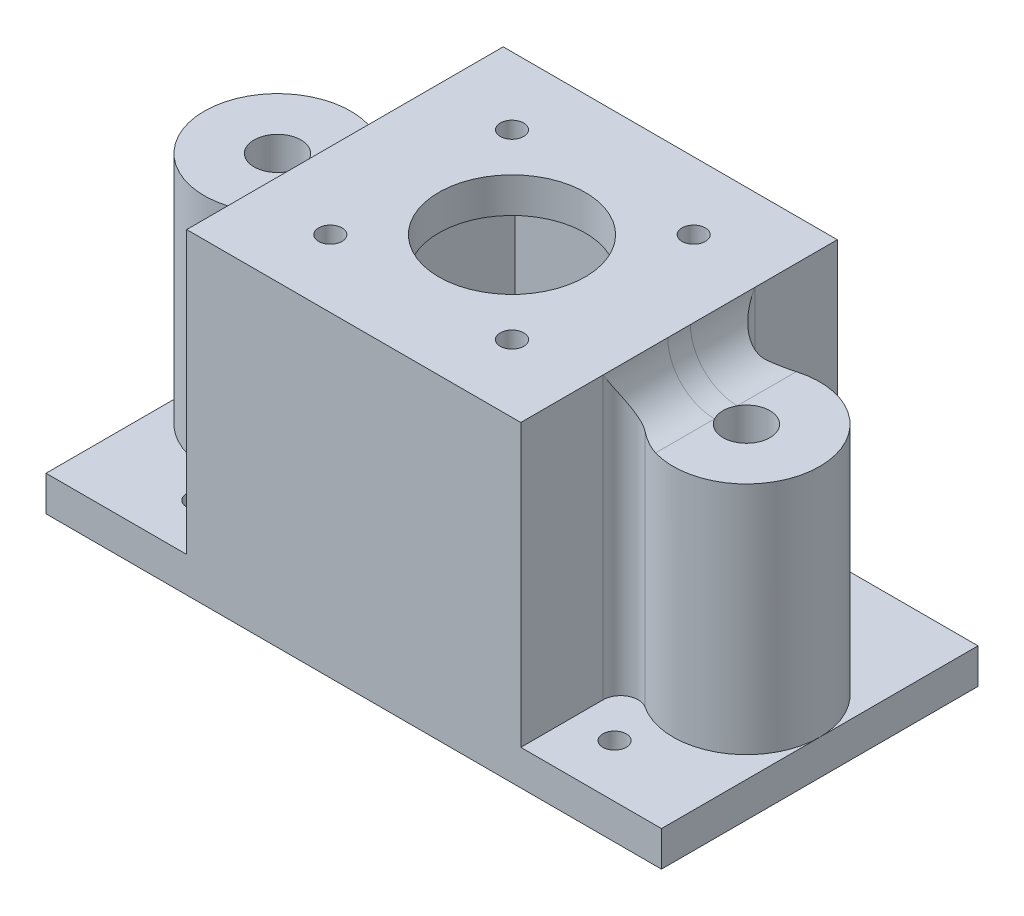
SolidWorks part; units mm, degrees
material "ABS"
ref_plane "Plano frontal" through (0, 0, 0) normal (0, 0, 1) x (1, 0, 0)
ref_plane "Plano superior" through (0, 0, 0) normal (0, 1, 0) x (1, 0, 0)
ref_plane "Plano direito" through (0, 0, 0) normal (1, 0, 0) x (0, 0, -1)
sketch "Esboço1" plane through (0, 0, 0) normal (0, 0, 1) x (1, 0, 0)
  line L0 (-28.5, 54) -> (28.5, 54)
  line L1 (28.5, 54) -> (28.5, 6)
  line L2 (52.5, 6) -> (28.5, 6)
  line L3 (52.5, 6) -> (52.5, 0)
  line L4 (52.5, 0) -> (22.5, 0)
  line L5 (22.5, 0) -> (22.5, 48)
  line L6 (22.5, 48) -> (-22.5, 48)
  line L7 (28.5, 6) -> (22.5, 6) construction
  line L8 (22.5, 48) -> (22.5, 54) construction
  line L9 (0, 63.425) -> (0, 0) construction
  line L10 (-22.5, 48) -> (-22.5, 54) construction
  line L11 (-28.5, 6) -> (-22.5, 6) construction
  line L12 (-22.5, 0) -> (-22.5, 48)
  line L13 (-52.5, 0) -> (-22.5, 0)
  line L14 (-52.5, 6) -> (-52.5, 0)
  line L15 (-52.5, 6) -> (-28.5, 6)
  line L16 (-28.5, 54) -> (-28.5, 6)
  point P19 (0, 48)
  point P23 (0, 54)
  dimension "D1" = 48
  dimension "D2" = 6
  dimension "D3" = 45
  dimension "D4" = 105
extrude "Ressalto-extrusão1" add sketch "Esboço1" along normal mid plane 54
sketch "Esboço2" plane through (0, 54, 0) normal (0, 1, 0) x (1, 0, 0)
  line L0 (0, 27) -> (0, -27) construction
  line L1 (28.5, 27) -> (-28.5, 27) construction
  line L2 (28.5, -27) -> (-28.5, -27) construction
  line L4 (-15.5, 15.5) -> (15.5, 15.5) construction
  line L5 (-15.5, 15.5) -> (-15.5, -15.5) construction
  line L6 (-15.5, -15.5) -> (15.5, -15.5) construction
  line L7 (15.5, 15.5) -> (15.5, -15.5) construction
  line L8 (-15.5, 15.5) -> (15.5, -15.5) construction
  line L9 (-15.5, -15.5) -> (15.5, 15.5) construction
  circle A0 centre (0, 0) radius 12.5
  circle A1 centre (-15.5, 15.5) radius 2
  circle A2 centre (15.5, 15.5) radius 2
  circle A3 centre (15.5, -15.5) radius 2
  circle A4 centre (-15.5, -15.5) radius 2
  dimension "D1" = 4
  dimension "D3" = 25
  dimension "D2" = 31
extrude "Corte-extrusão1" cut sketch "Esboço2" against normal blind 42
sketch "Esboço3" plane through (0, 6, 0) normal (0, 1, 0) x (1, 0, 0)
  line L0 (27.7526, 2.5) -> (28.5, 2.5)
  line L2 (0, 35.3204) -> (0, -32.8451) construction
  line L3 (0, 0) -> (71.2121, 0) construction
  line L4 (27.7526, -2.5) -> (28.5, -2.5)
  line L6 (28.5, -2.5) -> (28.5, 2.5)
  line L7 (-27.7526, -2.5) -> (-28.5, -2.5)
  line L8 (-28.5, -2.5) -> (-28.5, 2.5)
  line L9 (-27.7526, 2.5) -> (-28.5, 2.5)
  line L10 (28.5, -27) -> (28.5, 27) construction
  arc A0 (27.7526, -2.5) -> (27.7526, 2.5) centre (40, 0) ccw
  circle A1 centre (40, 0) radius 4
  circle A2 centre (-40, 0) radius 4
  arc A3 (-27.7526, -2.5) -> (-27.7526, 2.5) centre (-40, 0) cw
  dimension "D2" = 25
  dimension "D3" = 8
  dimension "D1" = 5
  dimension "D4" = 40
extrude "Ressalto-extrusão2" add sketch "Esboço3" along normal blind 40
fillet "Filete1" radius 8 2 edges at (-28.5, 46, 0) (28.5, 46, 0)
sketch "Esboço4" plane through (0, 6, 0) normal (0, 1, 0) x (1, 0, 0)
  line L0 (-35.5, 18) -> (-35.5, 27) construction
  line L1 (-28.5, 27) -> (-52.5, 27) construction
  line L2 (-35.5, 18) -> (-52.5, 18) construction
  line L3 (-52.5, -27) -> (-52.5, 0) construction
  line L4 (-59.6325, 0) -> (0, 0) construction
  line L5 (0, 0) -> (0, 35.3341) construction
  circle A0 centre (-35.5, 18) radius 2
  circle A1 centre (-35.5, 18) radius 5.5 construction
  circle A2 centre (35.5, 18) radius 2
  circle A3 centre (35.5, -18) radius 2
  circle A4 centre (-35.5, -18) radius 2
  dimension "D1" = 4
  dimension "D2" = 11
  dimension "D3" = 9
  dimension "D4" = 17
extrude "Corte-extrusão2" cut sketch "Esboço4" against normal through all
fillet "Filete5" radius 3 4 edges at (-28.5, 30, -4.899) (-28.5, 30, 4.899) (28.5, 30, -4.899) (28.5, 30, 4.899)
sketch "Esboço5" plane through (0, 0, 0) normal (0, -1, 0) x (1, 0, 0)
  line L0 (-22.5, 27) -> (22.5, 27)
  line L1 (22.5, 27) -> (22.5, 23)
  line L2 (22.5, 27) -> (22.5, -27) construction
  line L3 (22.5, 23) -> (-22.5, 23)
  line L4 (-22.5, 27) -> (-22.5, -27) construction
  line L5 (-22.5, 23) -> (-22.5, 27)
  line L6 (-22.5, 0) -> (25.9689, 0) construction
  line L7 (-22.5, 27) -> (-22.5, -27) construction
  line L8 (-22.5, -23) -> (-22.5, -27)
  line L9 (22.5, -23) -> (-22.5, -23)
  line L10 (22.5, -27) -> (22.5, -23)
  line L11 (-22.5, -27) -> (22.5, -27)
  dimension "D1" = 4
extrude "Ressalto-extrusão3" add sketch "Esboço5" against normal up to surface (48 mm away) up to face at (-15.5, 48, -13.5)
